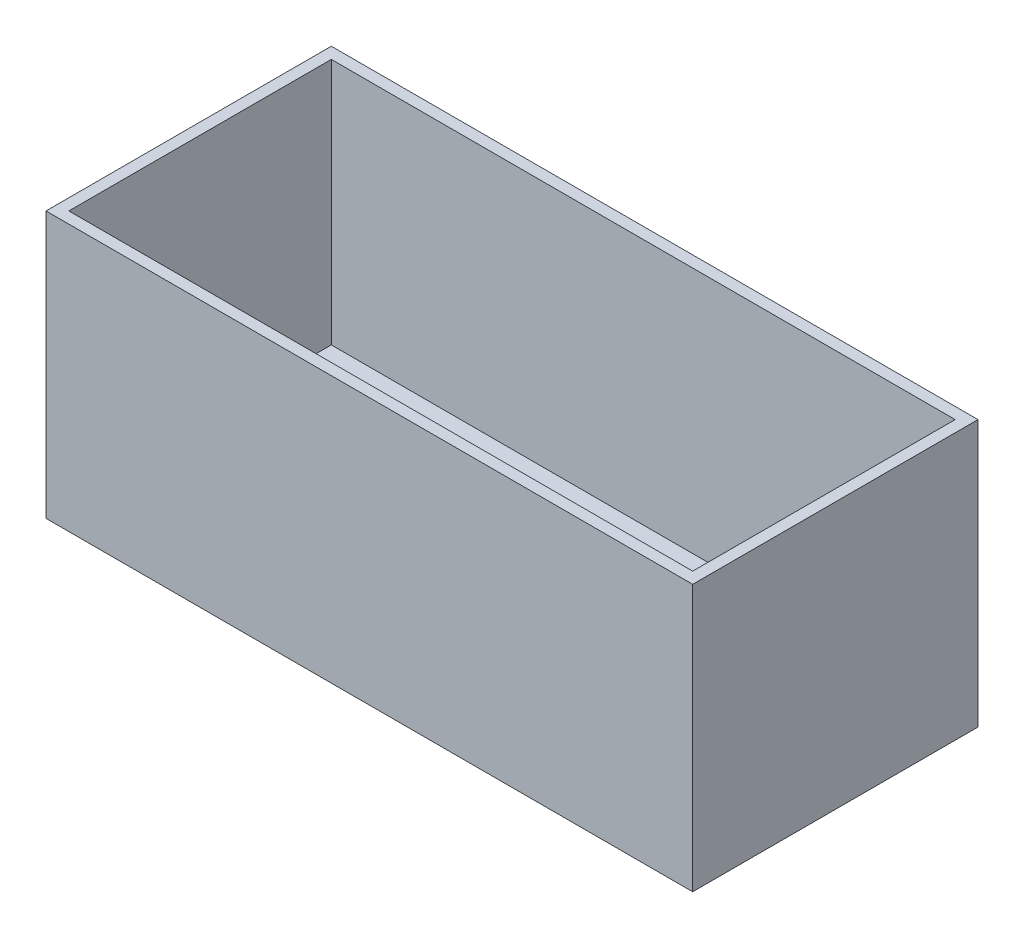
SolidWorks part; units mm, degrees
ref_plane "Front Plane" through (0, 0, 0) normal (0, 0, 1) x (1, 0, 0)
ref_plane "Top Plane" through (0, 0, 0) normal (0, 1, 0) x (1, 0, 0)
ref_plane "Right Plane" through (0, 0, 0) normal (1, 0, 0) x (0, 0, -1)
sketch "Sketch2" plane through (0, 0, 0) normal (0, 1, 0) x (1, 0, 0)
  line L0 (0, 45.9507) -> (0, -46.4585) construction
  line L1 (-85, 37.5) -> (85, 37.5)
  line L2 (-85, 37.5) -> (-85, -37.5)
  line L3 (-85, -37.5) -> (85, -37.5)
  line L4 (85, 37.5) -> (85, -37.5)
  line L5 (-100.5331, 0) -> (95.9634, 0) construction
  line L6 (-70.25, -6.5) -> (70.25, -6.5) construction
  line L7 (-70.25, 18.5) -> (70.25, 18.5)
  line L8 (-70.25, 18.5) -> (-70.25, -31.5)
  line L9 (-70.25, -31.5) -> (70.25, -31.5)
  line L10 (70.25, 18.5) -> (70.25, -31.5)
  circle A0 centre (-67.65, 14.9) radius 2.2
  circle A1 centre (67.65, 14.9) radius 2.2
  circle A4 centre (67.65, -27.9) radius 2.2
  circle A5 centre (-67.65, -27.9) radius 2.2
  point P0 (0, 0)
  point P24 (0, 0)
  dimension "D6" = 4.4
  dimension "D1" = 75
  dimension "D2" = 170
  dimension "D3" = 50
  dimension "D4" = 140.5
  dimension "D5" = 6
  dimension "D7" = 2.6
  dimension "D8" = 3.6
extrude "Boss-Extrude2" add sketch "Sketch2" along normal blind 5 contours L3 L4 L1 L2
extrude "Extrude-Thin1" add sketch "Sketch2<3>" along normal blind 65 from surface thin contours L2 L3 L4 L1 starting at face at (0, 5, 0) thin type one direction reverse wall 3
sketch "Sketch2<3>" plane through (0, 0, 0) normal (0, 1, 0) x (1, 0, 0) same geometry as "Sketch2"
extrude "Cut-Extrude1" cut sketch "Sketch2<6>" along normal blind 6 contours A0 | A5 | A1 | A4
sketch "Sketch2<6>" plane through (0, 0, 0) normal (0, 1, 0) x (1, 0, 0) same geometry as "Sketch2"
